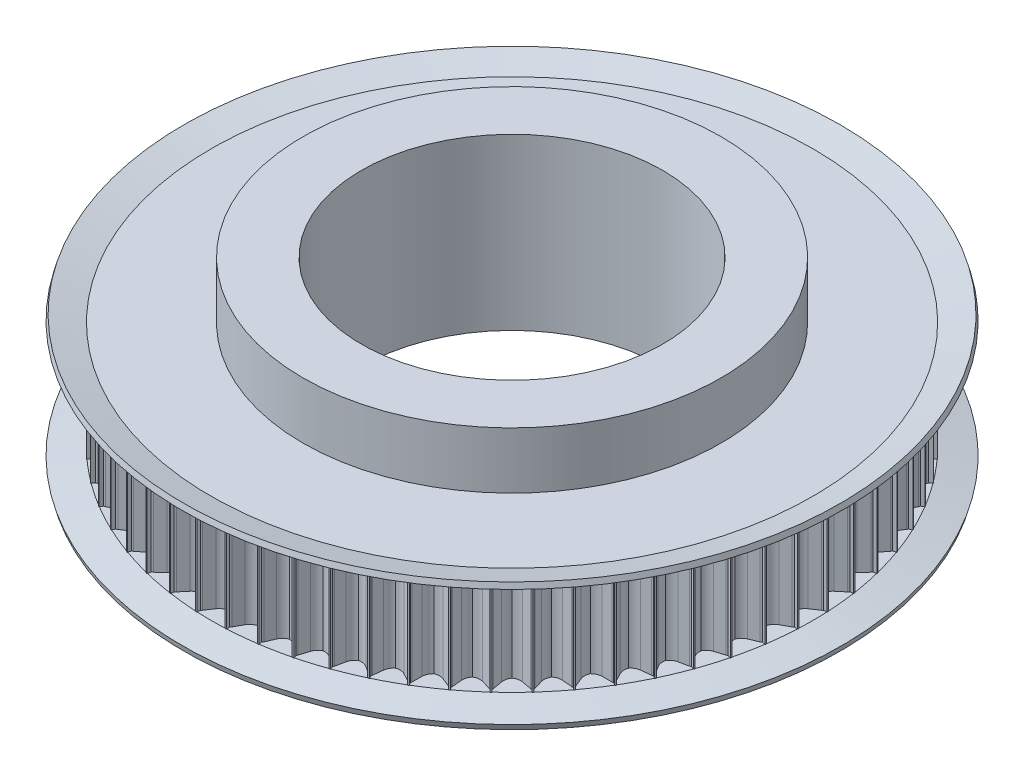
SolidWorks part; units mm, degrees
ref_plane "Front Plane" through (0, 0, 0) normal (0, 0, 1) x (1, 0, 0)
ref_plane "Top Plane" through (0, 0, 0) normal (0, 1, 0) x (1, 0, 0)
ref_plane "Right Plane" through (0, 0, 0) normal (1, 0, 0) x (0, 0, -1)
sketch "Sketch1" plane through (0, 0, 0) normal (0, 1, 0) x (1, 0, 0)
  circle A0 centre (0, 0) radius 40
  circle A1 centre (0, 0) radius 80
  dimension "D1" = 80
  dimension "D2" = 160
extrude "Boss-Extrude1" add sketch "Sketch1" along normal blind 27
sketch "Sketch2" plane through (0, 27, 0) normal (0, 1, 0) x (1, 0, 0)
  line L0 (0, 0) -> (82.1486, 0) construction
  line L8 (76.5582, 2.0076) -> (78.6891, 3.4656)
  line L9 (76.5582, -2.0076) -> (78.6891, -3.4656)
  line L10 (79, 3.75) -> (81.3566, 3.75)
  line L11 (81.3566, 3.75) -> (81.3566, -3.75)
  line L12 (81.3566, -3.75) -> (79, -3.75)
  line L13 (76.3863, -5.5061) -> (78.6499, -4.264)
  line L14 (75.9928, -9.5019) -> (77.9705, -11.1618)
  line L15 (78.9872, -4.0114) -> (81.3324, -4.2424)
  line L16 (81.3324, -4.2424) -> (80.5973, -11.7063)
  line L17 (80.5973, -11.7063) -> (78.252, -11.4753)
  line L18 (75.4788, -12.9667) -> (77.8532, -11.9525)
  line L19 (74.6955, -16.9048) -> (76.501, -18.7505)
  line L20 (78.2136, -11.7342) -> (80.525, -12.1939)
  line L21 (80.525, -12.1939) -> (79.0618, -19.5498)
  line L22 (79.0618, -19.5498) -> (76.7504, -19.0901)
  line L23 (73.8444, -20.3025) -> (76.3068, -19.5259)
  line L24 (72.6789, -24.1448) -> (74.2948, -26.1586)
  line L25 (76.6869, -19.344) -> (78.942, -20.0281)
  line L26 (78.942, -20.0281) -> (76.7649, -27.2051)
  line L27 (76.7649, -27.2051) -> (74.5097, -26.521)
  line L28 (71.4988, -27.4428) -> (74.0255, -26.9112)
  line L29 (69.9623, -31.1523) -> (71.373, -33.3148)
  line L30 (74.4215, -26.7674) -> (76.5988, -27.6693)
  line L31 (76.5988, -27.6693) -> (73.7287, -34.5984)
  line L32 (73.7287, -34.5984) -> (71.5514, -33.6965)
  line L33 (68.4647, -34.3187) -> (71.0313, -34.0374)
  line L34 (66.5719, -37.8598) -> (67.7639, -40.1502)
  line L35 (71.4395, -33.9331) -> (73.5179, -35.044)
  line L36 (73.5179, -35.044) -> (69.9824, -41.6584)
  line L37 (69.9824, -41.6584) -> (67.904, -40.5475)
  line L38 (64.7712, -40.8642) -> (67.353, -40.8358)
  line L39 (62.5405, -44.2027) -> (63.5022, -46.5989)
  line L40 (67.7695, -40.772) -> (69.7289, -42.0813)
  line L41 (69.7289, -42.0813) -> (65.5622, -48.3173)
  line L42 (65.5622, -48.3173) -> (63.6027, -47.0081)
  line L43 (60.4539, -47.0161) -> (63.0261, -47.2409)
  line L44 (57.9067, -50.1199) -> (58.629, -52.5988)
  line L45 (63.4468, -47.2183) -> (65.2685, -48.7133)
  line L46 (65.2685, -48.7133) -> (60.5105, -54.5109)
  line L47 (60.5105, -54.5109) -> (58.6889, -53.0159)
  line L48 (55.5544, -52.7152) -> (58.0922, -53.1911)
  line L49 (52.7152, -55.5544) -> (53.1911, -58.0922)
  line L50 (58.5131, -53.2098) -> (60.1795, -54.8762)
  line L51 (60.1795, -54.8762) -> (54.8762, -60.1795)
  line L52 (54.8762, -60.1795) -> (53.2098, -58.5131)
  line L53 (50.1199, -57.9067) -> (52.5988, -58.629)
  line L54 (47.0161, -60.4539) -> (47.2409, -63.0261)
  line L55 (53.0159, -58.6889) -> (54.5109, -60.5105)
  line L56 (54.5109, -60.5105) -> (48.7133, -65.2685)
  line L57 (48.7133, -65.2685) -> (47.2183, -63.4468)
  line L58 (44.2027, -62.5405) -> (46.5989, -63.5022)
  line L59 (40.8642, -64.7712) -> (40.8358, -67.353)
  line L60 (47.0081, -63.6027) -> (48.3173, -65.5622)
  line L61 (48.3173, -65.5622) -> (42.0813, -69.7289)
  line L62 (42.0813, -69.7289) -> (40.772, -67.7695)
  line L63 (37.8598, -66.5719) -> (40.1502, -67.7639)
  line L64 (34.3187, -68.4647) -> (34.0374, -71.0313)
  line L65 (40.5475, -67.904) -> (41.6584, -69.9824)
  line L66 (41.6584, -69.9824) -> (35.044, -73.5179)
  line L67 (35.044, -73.5179) -> (33.9331, -71.4395)
  line L68 (31.1523, -69.9623) -> (33.3148, -71.373)
  line L69 (27.4428, -71.4988) -> (26.9112, -74.0255)
  line L70 (33.6965, -71.5514) -> (34.5984, -73.7287)
  line L71 (34.5984, -73.7287) -> (27.6693, -76.5988)
  line L72 (27.6693, -76.5988) -> (26.7674, -74.4215)
  line L73 (24.1448, -72.6789) -> (26.1586, -74.2948)
  line L74 (20.3025, -73.8444) -> (19.5259, -76.3068)
  line L75 (26.521, -74.5097) -> (27.2051, -76.7649)
  line L76 (27.2051, -76.7649) -> (20.0281, -78.942)
  line L77 (20.0281, -78.942) -> (19.344, -76.6869)
  line L78 (16.9048, -74.6955) -> (18.7505, -76.501)
  line L79 (12.9667, -75.4788) -> (11.9525, -77.8532)
  line L80 (19.0901, -76.7504) -> (19.5498, -79.0618)
  line L81 (19.5498, -79.0618) -> (12.1939, -80.525)
  line L82 (12.1939, -80.525) -> (11.7342, -78.2136)
  line L83 (9.5019, -75.9928) -> (11.1618, -77.9705)
  line L84 (5.5061, -76.3863) -> (4.264, -78.6499)
  line L85 (11.4753, -78.252) -> (11.7063, -80.5973)
  line L86 (11.7063, -80.5973) -> (4.2424, -81.3324)
  line L87 (4.2424, -81.3324) -> (4.0114, -78.9872)
  line L88 (2.0076, -76.5582) -> (3.4656, -78.6891)
  line L89 (-2.0076, -76.5582) -> (-3.4656, -78.6891)
  line L90 (3.75, -79) -> (3.75, -81.3566)
  line L91 (3.75, -81.3566) -> (-3.75, -81.3566)
  line L92 (-3.75, -81.3566) -> (-3.75, -79)
  line L93 (-5.5061, -76.3863) -> (-4.264, -78.6499)
  line L94 (-9.5019, -75.9928) -> (-11.1618, -77.9705)
  line L95 (-4.0114, -78.9872) -> (-4.2424, -81.3324)
  line L96 (-4.2424, -81.3324) -> (-11.7063, -80.5973)
  line L97 (-11.7063, -80.5973) -> (-11.4753, -78.252)
  line L98 (-12.9667, -75.4788) -> (-11.9525, -77.8532)
  line L99 (-16.9048, -74.6955) -> (-18.7505, -76.501)
  line L100 (-11.7342, -78.2136) -> (-12.1939, -80.525)
  line L101 (-12.1939, -80.525) -> (-19.5498, -79.0618)
  line L102 (-19.5498, -79.0618) -> (-19.0901, -76.7504)
  line L103 (-20.3025, -73.8444) -> (-19.5259, -76.3068)
  line L104 (-24.1448, -72.6789) -> (-26.1586, -74.2948)
  line L105 (-19.344, -76.6869) -> (-20.0281, -78.942)
  line L106 (-20.0281, -78.942) -> (-27.2051, -76.7649)
  line L107 (-27.2051, -76.7649) -> (-26.521, -74.5097)
  line L108 (-27.4428, -71.4988) -> (-26.9112, -74.0255)
  line L109 (-31.1523, -69.9623) -> (-33.3148, -71.373)
  line L110 (-26.7674, -74.4215) -> (-27.6693, -76.5988)
  line L111 (-27.6693, -76.5988) -> (-34.5984, -73.7287)
  line L112 (-34.5984, -73.7287) -> (-33.6965, -71.5514)
  line L113 (-34.3187, -68.4647) -> (-34.0374, -71.0313)
  line L114 (-37.8598, -66.5719) -> (-40.1502, -67.7639)
  line L115 (-33.9331, -71.4395) -> (-35.044, -73.5179)
  line L116 (-35.044, -73.5179) -> (-41.6584, -69.9824)
  line L117 (-41.6584, -69.9824) -> (-40.5475, -67.904)
  line L118 (-40.8642, -64.7712) -> (-40.8358, -67.353)
  line L119 (-44.2027, -62.5405) -> (-46.5989, -63.5022)
  line L120 (-40.772, -67.7695) -> (-42.0813, -69.7289)
  line L121 (-42.0813, -69.7289) -> (-48.3173, -65.5622)
  line L122 (-48.3173, -65.5622) -> (-47.0081, -63.6027)
  line L123 (-47.0161, -60.4539) -> (-47.2409, -63.0261)
  line L124 (-50.1199, -57.9067) -> (-52.5988, -58.629)
  line L125 (-47.2183, -63.4468) -> (-48.7133, -65.2685)
  line L126 (-48.7133, -65.2685) -> (-54.5109, -60.5105)
  line L127 (-54.5109, -60.5105) -> (-53.0159, -58.6889)
  line L128 (-52.7152, -55.5544) -> (-53.1911, -58.0922)
  line L129 (-55.5544, -52.7152) -> (-58.0922, -53.1911)
  line L130 (-53.2098, -58.5131) -> (-54.8762, -60.1795)
  line L131 (-54.8762, -60.1795) -> (-60.1795, -54.8762)
  line L132 (-60.1795, -54.8762) -> (-58.5131, -53.2098)
  line L133 (-57.9067, -50.1199) -> (-58.629, -52.5988)
  line L134 (-60.4539, -47.0161) -> (-63.0261, -47.2409)
  line L135 (-58.6889, -53.0159) -> (-60.5105, -54.5109)
  line L136 (-60.5105, -54.5109) -> (-65.2685, -48.7133)
  line L137 (-65.2685, -48.7133) -> (-63.4468, -47.2183)
  line L138 (-62.5405, -44.2027) -> (-63.5022, -46.5989)
  line L139 (-64.7712, -40.8642) -> (-67.353, -40.8358)
  line L140 (-63.6027, -47.0081) -> (-65.5622, -48.3173)
  line L141 (-65.5622, -48.3173) -> (-69.7289, -42.0813)
  line L142 (-69.7289, -42.0813) -> (-67.7695, -40.772)
  line L143 (-66.5719, -37.8598) -> (-67.7639, -40.1502)
  line L144 (-68.4647, -34.3187) -> (-71.0313, -34.0374)
  line L145 (-67.904, -40.5475) -> (-69.9824, -41.6584)
  line L146 (-69.9824, -41.6584) -> (-73.5179, -35.044)
  line L147 (-73.5179, -35.044) -> (-71.4395, -33.9331)
  line L148 (-69.9623, -31.1523) -> (-71.373, -33.3148)
  line L149 (-71.4988, -27.4428) -> (-74.0255, -26.9112)
  line L150 (-71.5514, -33.6965) -> (-73.7287, -34.5984)
  line L151 (-73.7287, -34.5984) -> (-76.5988, -27.6693)
  line L152 (-76.5988, -27.6693) -> (-74.4215, -26.7674)
  line L153 (-72.6789, -24.1448) -> (-74.2948, -26.1586)
  line L154 (-73.8444, -20.3025) -> (-76.3068, -19.5259)
  line L155 (-74.5097, -26.521) -> (-76.7649, -27.2051)
  line L156 (-76.7649, -27.2051) -> (-78.942, -20.0281)
  line L157 (-78.942, -20.0281) -> (-76.6869, -19.344)
  line L158 (-74.6955, -16.9048) -> (-76.501, -18.7505)
  line L159 (-75.4788, -12.9667) -> (-77.8532, -11.9525)
  line L160 (-76.7504, -19.0901) -> (-79.0618, -19.5498)
  line L161 (-79.0618, -19.5498) -> (-80.525, -12.1939)
  line L162 (-80.525, -12.1939) -> (-78.2136, -11.7342)
  line L163 (-75.9928, -9.5019) -> (-77.9705, -11.1618)
  line L164 (-76.3863, -5.5061) -> (-78.6499, -4.264)
  line L165 (-78.252, -11.4753) -> (-80.5973, -11.7063)
  line L166 (-80.5973, -11.7063) -> (-81.3324, -4.2424)
  line L167 (-81.3324, -4.2424) -> (-78.9872, -4.0114)
  line L168 (-76.5582, -2.0076) -> (-78.6891, -3.4656)
  line L169 (-76.5582, 2.0076) -> (-78.6891, 3.4656)
  line L170 (-79, -3.75) -> (-81.3566, -3.75)
  line L171 (-81.3566, -3.75) -> (-81.3566, 3.75)
  line L172 (-81.3566, 3.75) -> (-79, 3.75)
  line L173 (-76.3863, 5.5061) -> (-78.6499, 4.264)
  line L174 (-75.9928, 9.5019) -> (-77.9705, 11.1618)
  line L175 (-78.9872, 4.0114) -> (-81.3324, 4.2424)
  line L176 (-81.3324, 4.2424) -> (-80.5973, 11.7063)
  line L177 (-80.5973, 11.7063) -> (-78.252, 11.4753)
  line L178 (-75.4788, 12.9667) -> (-77.8532, 11.9525)
  line L179 (-74.6955, 16.9048) -> (-76.501, 18.7505)
  line L180 (-78.2136, 11.7342) -> (-80.525, 12.1939)
  line L181 (-80.525, 12.1939) -> (-79.0618, 19.5498)
  line L182 (-79.0618, 19.5498) -> (-76.7504, 19.0901)
  line L183 (-73.8444, 20.3025) -> (-76.3068, 19.5259)
  line L184 (-72.6789, 24.1448) -> (-74.2948, 26.1586)
  line L185 (-76.6869, 19.344) -> (-78.942, 20.0281)
  line L186 (-78.942, 20.0281) -> (-76.7649, 27.2051)
  line L187 (-76.7649, 27.2051) -> (-74.5097, 26.521)
  line L188 (-71.4988, 27.4428) -> (-74.0255, 26.9112)
  line L189 (-69.9623, 31.1523) -> (-71.373, 33.3148)
  line L190 (-74.4215, 26.7674) -> (-76.5988, 27.6693)
  line L191 (-76.5988, 27.6693) -> (-73.7287, 34.5984)
  line L192 (-73.7287, 34.5984) -> (-71.5514, 33.6965)
  line L193 (-68.4647, 34.3187) -> (-71.0313, 34.0374)
  line L194 (-66.5719, 37.8598) -> (-67.7639, 40.1502)
  line L195 (-71.4395, 33.9331) -> (-73.5179, 35.044)
  line L196 (-73.5179, 35.044) -> (-69.9824, 41.6584)
  line L197 (-69.9824, 41.6584) -> (-67.904, 40.5475)
  line L198 (-64.7712, 40.8642) -> (-67.353, 40.8358)
  line L199 (-62.5405, 44.2027) -> (-63.5022, 46.5989)
  line L200 (-67.7695, 40.772) -> (-69.7289, 42.0813)
  line L201 (-69.7289, 42.0813) -> (-65.5622, 48.3173)
  line L202 (-65.5622, 48.3173) -> (-63.6027, 47.0081)
  line L203 (-60.4539, 47.0161) -> (-63.0261, 47.2409)
  line L204 (-57.9067, 50.1199) -> (-58.629, 52.5988)
  line L205 (-63.4468, 47.2183) -> (-65.2685, 48.7133)
  line L206 (-65.2685, 48.7133) -> (-60.5105, 54.5109)
  line L207 (-60.5105, 54.5109) -> (-58.6889, 53.0159)
  line L208 (-55.5544, 52.7152) -> (-58.0922, 53.1911)
  line L209 (-52.7152, 55.5544) -> (-53.1911, 58.0922)
  line L210 (-58.5131, 53.2098) -> (-60.1795, 54.8762)
  line L211 (-60.1795, 54.8762) -> (-54.8762, 60.1795)
  line L212 (-54.8762, 60.1795) -> (-53.2098, 58.5131)
  line L213 (-50.1199, 57.9067) -> (-52.5988, 58.629)
  line L214 (-47.0161, 60.4539) -> (-47.2409, 63.0261)
  line L215 (-53.0159, 58.6889) -> (-54.5109, 60.5105)
  line L216 (-54.5109, 60.5105) -> (-48.7133, 65.2685)
  line L217 (-48.7133, 65.2685) -> (-47.2183, 63.4468)
  line L218 (-44.2027, 62.5405) -> (-46.5989, 63.5022)
  line L219 (-40.8642, 64.7712) -> (-40.8358, 67.353)
  line L220 (-47.0081, 63.6027) -> (-48.3173, 65.5622)
  line L221 (-48.3173, 65.5622) -> (-42.0813, 69.7289)
  line L222 (-42.0813, 69.7289) -> (-40.772, 67.7695)
  line L223 (-37.8598, 66.5719) -> (-40.1502, 67.7639)
  line L224 (-34.3187, 68.4647) -> (-34.0374, 71.0313)
  line L225 (-40.5475, 67.904) -> (-41.6584, 69.9824)
  line L226 (-41.6584, 69.9824) -> (-35.044, 73.5179)
  line L227 (-35.044, 73.5179) -> (-33.9331, 71.4395)
  line L228 (-31.1523, 69.9623) -> (-33.3148, 71.373)
  line L229 (-27.4428, 71.4988) -> (-26.9112, 74.0255)
  line L230 (-33.6965, 71.5514) -> (-34.5984, 73.7287)
  line L231 (-34.5984, 73.7287) -> (-27.6693, 76.5988)
  line L232 (-27.6693, 76.5988) -> (-26.7674, 74.4215)
  line L233 (-24.1448, 72.6789) -> (-26.1586, 74.2948)
  line L234 (-20.3025, 73.8444) -> (-19.5259, 76.3068)
  line L235 (-26.521, 74.5097) -> (-27.2051, 76.7649)
  line L236 (-27.2051, 76.7649) -> (-20.0281, 78.942)
  line L237 (-20.0281, 78.942) -> (-19.344, 76.6869)
  line L238 (-16.9048, 74.6955) -> (-18.7505, 76.501)
  line L239 (-12.9667, 75.4788) -> (-11.9525, 77.8532)
  line L240 (-19.0901, 76.7504) -> (-19.5498, 79.0618)
  line L241 (-19.5498, 79.0618) -> (-12.1939, 80.525)
  line L242 (-12.1939, 80.525) -> (-11.7342, 78.2136)
  line L243 (-9.5019, 75.9928) -> (-11.1618, 77.9705)
  line L244 (-5.5061, 76.3863) -> (-4.264, 78.6499)
  line L245 (-11.4753, 78.252) -> (-11.7063, 80.5973)
  line L246 (-11.7063, 80.5973) -> (-4.2424, 81.3324)
  line L247 (-4.2424, 81.3324) -> (-4.0114, 78.9872)
  line L248 (-2.0076, 76.5582) -> (-3.4656, 78.6891)
  line L249 (2.0076, 76.5582) -> (3.4656, 78.6891)
  line L250 (-3.75, 79) -> (-3.75, 81.3566)
  line L251 (-3.75, 81.3566) -> (3.75, 81.3566)
  line L252 (3.75, 81.3566) -> (3.75, 79)
  line L253 (5.5061, 76.3863) -> (4.264, 78.6499)
  line L254 (9.5019, 75.9928) -> (11.1618, 77.9705)
  line L255 (4.0114, 78.9872) -> (4.2424, 81.3324)
  line L256 (4.2424, 81.3324) -> (11.7063, 80.5973)
  line L257 (11.7063, 80.5973) -> (11.4753, 78.252)
  line L258 (12.9667, 75.4788) -> (11.9525, 77.8532)
  line L259 (16.9048, 74.6955) -> (18.7505, 76.501)
  line L260 (11.7342, 78.2136) -> (12.1939, 80.525)
  line L261 (12.1939, 80.525) -> (19.5498, 79.0618)
  line L262 (19.5498, 79.0618) -> (19.0901, 76.7504)
  line L263 (20.3025, 73.8444) -> (19.5259, 76.3068)
  line L264 (24.1448, 72.6789) -> (26.1586, 74.2948)
  line L265 (19.344, 76.6869) -> (20.0281, 78.942)
  line L266 (20.0281, 78.942) -> (27.2051, 76.7649)
  line L267 (27.2051, 76.7649) -> (26.521, 74.5097)
  line L268 (27.4428, 71.4988) -> (26.9112, 74.0255)
  line L269 (31.1523, 69.9623) -> (33.3148, 71.373)
  line L270 (26.7674, 74.4215) -> (27.6693, 76.5988)
  line L271 (27.6693, 76.5988) -> (34.5984, 73.7287)
  line L272 (34.5984, 73.7287) -> (33.6965, 71.5514)
  line L273 (34.3187, 68.4647) -> (34.0374, 71.0313)
  line L274 (37.8598, 66.5719) -> (40.1502, 67.7639)
  line L275 (33.9331, 71.4395) -> (35.044, 73.5179)
  line L276 (35.044, 73.5179) -> (41.6584, 69.9824)
  line L277 (41.6584, 69.9824) -> (40.5475, 67.904)
  line L278 (40.8642, 64.7712) -> (40.8358, 67.353)
  line L279 (44.2027, 62.5405) -> (46.5989, 63.5022)
  line L280 (40.772, 67.7695) -> (42.0813, 69.7289)
  line L281 (42.0813, 69.7289) -> (48.3173, 65.5622)
  line L282 (48.3173, 65.5622) -> (47.0081, 63.6027)
  line L283 (47.0161, 60.4539) -> (47.2409, 63.0261)
  line L284 (50.1199, 57.9067) -> (52.5988, 58.629)
  line L285 (47.2183, 63.4468) -> (48.7133, 65.2685)
  line L286 (48.7133, 65.2685) -> (54.5109, 60.5105)
  line L287 (54.5109, 60.5105) -> (53.0159, 58.6889)
  line L288 (52.7152, 55.5544) -> (53.1911, 58.0922)
  line L289 (55.5544, 52.7152) -> (58.0922, 53.1911)
  line L290 (53.2098, 58.5131) -> (54.8762, 60.1795)
  line L291 (54.8762, 60.1795) -> (60.1795, 54.8762)
  line L292 (60.1795, 54.8762) -> (58.5131, 53.2098)
  line L293 (57.9067, 50.1199) -> (58.629, 52.5988)
  line L294 (60.4539, 47.0161) -> (63.0261, 47.2409)
  line L295 (58.6889, 53.0159) -> (60.5105, 54.5109)
  line L296 (60.5105, 54.5109) -> (65.2685, 48.7133)
  line L297 (65.2685, 48.7133) -> (63.4468, 47.2183)
  line L298 (62.5405, 44.2027) -> (63.5022, 46.5989)
  line L299 (64.7712, 40.8642) -> (67.353, 40.8358)
  line L300 (63.6027, 47.0081) -> (65.5622, 48.3173)
  line L301 (65.5622, 48.3173) -> (69.7289, 42.0813)
  line L302 (69.7289, 42.0813) -> (67.7695, 40.772)
  line L303 (66.5719, 37.8598) -> (67.7639, 40.1502)
  line L304 (68.4647, 34.3187) -> (71.0313, 34.0374)
  line L305 (67.904, 40.5475) -> (69.9824, 41.6584)
  line L306 (69.9824, 41.6584) -> (73.5179, 35.044)
  line L307 (73.5179, 35.044) -> (71.4395, 33.9331)
  line L308 (69.9623, 31.1523) -> (71.373, 33.3148)
  line L309 (71.4988, 27.4428) -> (74.0255, 26.9112)
  line L310 (71.5514, 33.6965) -> (73.7287, 34.5984)
  line L311 (73.7287, 34.5984) -> (76.5988, 27.6693)
  line L312 (76.5988, 27.6693) -> (74.4215, 26.7674)
  line L313 (72.6789, 24.1448) -> (74.2948, 26.1586)
  line L314 (73.8444, 20.3025) -> (76.3068, 19.5259)
  line L315 (74.5097, 26.521) -> (76.7649, 27.2051)
  line L316 (76.7649, 27.2051) -> (78.942, 20.0281)
  line L317 (78.942, 20.0281) -> (76.6869, 19.344)
  line L318 (74.6955, 16.9048) -> (76.501, 18.7505)
  line L319 (75.4788, 12.9667) -> (77.8532, 11.9525)
  line L320 (76.7504, 19.0901) -> (79.0618, 19.5498)
  line L321 (79.0618, 19.5498) -> (80.525, 12.1939)
  line L322 (80.525, 12.1939) -> (78.2136, 11.7342)
  line L323 (75.9928, 9.5019) -> (77.9705, 11.1618)
  line L324 (76.3863, 5.5061) -> (78.6499, 4.264)
  line L325 (78.252, 11.4753) -> (80.5973, 11.7063)
  line L326 (80.5973, 11.7063) -> (81.3324, 4.2424)
  line L327 (81.3324, 4.2424) -> (78.9872, 4.0114)
  arc A4 (75.289, 0) -> (76.5582, -2.0076) centre (78.2523, 0.4683) ccw
  arc A5 (79, -3.75) -> (78.6891, -3.4656) centre (77.8421, -4.7036) ccw
  arc A6 (79, 3.75) -> (78.6891, 3.4656) centre (77.8421, 4.7036) cw
  arc A7 (75.289, 0) -> (76.5582, 2.0076) centre (78.2523, -0.4683) cw
  arc A8 (74.9265, -7.3796) -> (75.9928, -9.5019) centre (77.9214, -7.204) ccw
  arc A9 (78.252, -11.4753) -> (77.9705, -11.1618) centre (77.0062, -12.3108) ccw
  arc A10 (78.9872, -4.0114) -> (78.6499, -4.264) centre (77.9283, -2.9489) cw
  arc A11 (74.9265, -7.3796) -> (76.3863, -5.5061) centre (77.8295, -8.1361) cw
  arc A12 (73.8424, -14.6882) -> (74.6955, -16.9048) centre (76.84, -14.8069) ccw
  arc A13 (76.7504, -19.0901) -> (76.501, -18.7505) centre (75.4288, -19.7994) ccw
  arc A14 (78.2136, -11.7342) -> (77.8532, -11.9525) centre (77.264, -10.5731) cw
  arc A15 (73.8424, -14.6882) -> (75.4788, -12.9667) centre (76.6573, -15.7256) cw
  arc A16 (72.0471, -21.8553) -> (72.6789, -24.1448) centre (75.0187, -22.2673) ccw
  arc A17 (74.5097, -26.521) -> (74.2948, -26.1586) centre (73.1249, -27.0974) ccw
  arc A18 (76.6869, -19.344) -> (76.3068, -19.5259) centre (75.8556, -18.0953) cw
  arc A19 (72.0471, -21.8553) -> (73.8444, -20.3025) centre (74.7468, -23.1636) cw
  arc A20 (69.558, -28.8119) -> (69.9623, -31.1523) centre (72.4749, -29.5132) ccw
  arc A21 (71.5514, -33.6965) -> (71.373, -33.3148) centre (70.1168, -34.1344) ccw
  arc A22 (74.4215, -26.7674) -> (74.0255, -26.9112) centre (73.7167, -25.4434) cw
  arc A23 (69.558, -28.8119) -> (71.4988, -27.4428) centre (72.1164, -30.3785) cw
  arc A24 (66.399, -35.491) -> (66.5719, -37.8598) centre (69.2331, -36.4748) ccw
  arc A25 (67.904, -40.5475) -> (67.7639, -40.1502) centre (66.4334, -40.8427) ccw
  arc A26 (71.4395, -33.9331) -> (71.0313, -34.0374) centre (70.8679, -32.5463) cw
  arc A27 (66.399, -35.491) -> (68.4647, -34.3187) centre (68.7916, -37.3009) cw
  arc A28 (62.6005, -41.8283) -> (62.5405, -44.2027) centre (65.3246, -43.0852) ccw
  arc A29 (63.6027, -47.0081) -> (63.5022, -46.5989) centre (62.1102, -47.1576) ccw
  arc A30 (67.7695, -40.772) -> (67.353, -40.8358) centre (67.3365, -39.3359) cw
  arc A31 (62.6005, -41.8283) -> (64.7712, -40.8642) centre (64.8042, -43.864) cw
  arc A32 (58.1992, -47.7629) -> (57.9067, -50.1199) centre (60.7869, -49.2807) ccw
  arc A33 (58.6889, -53.0159) -> (58.629, -52.5988) centre (57.1889, -53.0184) ccw
  arc A34 (63.4468, -47.2183) -> (63.0261, -47.2409) centre (63.1567, -45.7466) cw
  arc A35 (58.1992, -47.7629) -> (60.4539, -47.0161) centre (60.1927, -50.0047) cw
  arc A36 (53.2374, -53.2374) -> (52.7152, -55.5544) centre (55.6639, -55.0015) ccw
  arc A37 (53.2098, -58.5131) -> (53.1911, -58.0922) centre (51.7168, -58.3686) ccw
  arc A38 (58.5131, -53.2098) -> (58.0922, -53.1911) centre (58.3686, -51.7168) cw
  arc A39 (53.2374, -53.2374) -> (55.5544, -52.7152) centre (55.0015, -55.6639) cw
  arc A40 (47.7629, -58.1992) -> (47.0161, -60.4539) centre (50.0047, -60.1927) ccw
  arc A41 (47.2183, -63.4468) -> (47.2409, -63.0261) centre (45.7466, -63.1567) ccw
  arc A42 (53.0159, -58.6889) -> (52.5988, -58.629) centre (53.0184, -57.1889) cw
  arc A43 (47.7629, -58.1992) -> (50.1199, -57.9067) centre (49.2807, -60.7869) cw
  arc A44 (41.8283, -62.6005) -> (40.8642, -64.7712) centre (43.864, -64.8042) ccw
  arc A45 (40.772, -67.7695) -> (40.8358, -67.353) centre (39.3359, -67.3365) ccw
  arc A46 (47.0081, -63.6027) -> (46.5989, -63.5022) centre (47.1576, -62.1102) cw
  arc A47 (41.8283, -62.6005) -> (44.2027, -62.5405) centre (43.0852, -65.3246) cw
  arc A48 (35.491, -66.399) -> (34.3187, -68.4647) centre (37.3009, -68.7916) ccw
  arc A49 (33.9331, -71.4395) -> (34.0374, -71.0313) centre (32.5463, -70.8679) ccw
  arc A50 (40.5475, -67.904) -> (40.1502, -67.7639) centre (40.8427, -66.4334) cw
  arc A51 (35.491, -66.399) -> (37.8598, -66.5719) centre (36.4748, -69.2331) cw
  arc A52 (28.8119, -69.558) -> (27.4428, -71.4988) centre (30.3785, -72.1164) ccw
  arc A53 (26.7674, -74.4215) -> (26.9112, -74.0255) centre (25.4434, -73.7167) ccw
  arc A54 (33.6965, -71.5514) -> (33.3148, -71.373) centre (34.1344, -70.1168) cw
  arc A55 (28.8119, -69.558) -> (31.1523, -69.9623) centre (29.5132, -72.4749) cw
  arc A56 (21.8553, -72.0471) -> (20.3025, -73.8444) centre (23.1636, -74.7468) ccw
  arc A57 (19.344, -76.6869) -> (19.5259, -76.3068) centre (18.0953, -75.8556) ccw
  arc A58 (26.521, -74.5097) -> (26.1586, -74.2948) centre (27.0974, -73.1249) cw
  arc A59 (21.8553, -72.0471) -> (24.1448, -72.6789) centre (22.2673, -75.0187) cw
  arc A60 (14.6882, -73.8424) -> (12.9667, -75.4788) centre (15.7256, -76.6573) ccw
  arc A61 (11.7342, -78.2136) -> (11.9525, -77.8532) centre (10.5731, -77.264) ccw
  arc A62 (19.0901, -76.7504) -> (18.7505, -76.501) centre (19.7994, -75.4288) cw
  arc A63 (14.6882, -73.8424) -> (16.9048, -74.6955) centre (14.8069, -76.84) cw
  arc A64 (7.3796, -74.9265) -> (5.5061, -76.3863) centre (8.1361, -77.8295) ccw
  arc A65 (4.0114, -78.9872) -> (4.264, -78.6499) centre (2.9489, -77.9283) ccw
  arc A66 (11.4753, -78.252) -> (11.1618, -77.9705) centre (12.3108, -77.0062) cw
  arc A67 (7.3796, -74.9265) -> (9.5019, -75.9928) centre (7.204, -77.9214) cw
  arc A68 (0, -75.289) -> (-2.0076, -76.5582) centre (0.4683, -78.2523) ccw
  arc A69 (-3.75, -79) -> (-3.4656, -78.6891) centre (-4.7036, -77.8421) ccw
  arc A70 (3.75, -79) -> (3.4656, -78.6891) centre (4.7036, -77.8421) cw
  arc A71 (0, -75.289) -> (2.0076, -76.5582) centre (-0.4683, -78.2523) cw
  arc A72 (-7.3796, -74.9265) -> (-9.5019, -75.9928) centre (-7.204, -77.9214) ccw
  arc A73 (-11.4753, -78.252) -> (-11.1618, -77.9705) centre (-12.3108, -77.0062) ccw
  arc A74 (-4.0114, -78.9872) -> (-4.264, -78.6499) centre (-2.9489, -77.9283) cw
  arc A75 (-7.3796, -74.9265) -> (-5.5061, -76.3863) centre (-8.1361, -77.8295) cw
  arc A76 (-14.6882, -73.8424) -> (-16.9048, -74.6955) centre (-14.8069, -76.84) ccw
  arc A77 (-19.0901, -76.7504) -> (-18.7505, -76.501) centre (-19.7994, -75.4288) ccw
  arc A78 (-11.7342, -78.2136) -> (-11.9525, -77.8532) centre (-10.5731, -77.264) cw
  arc A79 (-14.6882, -73.8424) -> (-12.9667, -75.4788) centre (-15.7256, -76.6573) cw
  arc A80 (-21.8553, -72.0471) -> (-24.1448, -72.6789) centre (-22.2673, -75.0187) ccw
  arc A81 (-26.521, -74.5097) -> (-26.1586, -74.2948) centre (-27.0974, -73.1249) ccw
  arc A82 (-19.344, -76.6869) -> (-19.5259, -76.3068) centre (-18.0953, -75.8556) cw
  arc A83 (-21.8553, -72.0471) -> (-20.3025, -73.8444) centre (-23.1636, -74.7468) cw
  arc A84 (-28.8119, -69.558) -> (-31.1523, -69.9623) centre (-29.5132, -72.4749) ccw
  arc A85 (-33.6965, -71.5514) -> (-33.3148, -71.373) centre (-34.1344, -70.1168) ccw
  arc A86 (-26.7674, -74.4215) -> (-26.9112, -74.0255) centre (-25.4434, -73.7167) cw
  arc A87 (-28.8119, -69.558) -> (-27.4428, -71.4988) centre (-30.3785, -72.1164) cw
  arc A88 (-35.491, -66.399) -> (-37.8598, -66.5719) centre (-36.4748, -69.2331) ccw
  arc A89 (-40.5475, -67.904) -> (-40.1502, -67.7639) centre (-40.8427, -66.4334) ccw
  arc A90 (-33.9331, -71.4395) -> (-34.0374, -71.0313) centre (-32.5463, -70.8679) cw
  arc A91 (-35.491, -66.399) -> (-34.3187, -68.4647) centre (-37.3009, -68.7916) cw
  arc A92 (-41.8283, -62.6005) -> (-44.2027, -62.5405) centre (-43.0852, -65.3246) ccw
  arc A93 (-47.0081, -63.6027) -> (-46.5989, -63.5022) centre (-47.1576, -62.1102) ccw
  arc A94 (-40.772, -67.7695) -> (-40.8358, -67.353) centre (-39.3359, -67.3365) cw
  arc A95 (-41.8283, -62.6005) -> (-40.8642, -64.7712) centre (-43.864, -64.8042) cw
  arc A96 (-47.7629, -58.1992) -> (-50.1199, -57.9067) centre (-49.2807, -60.7869) ccw
  arc A97 (-53.0159, -58.6889) -> (-52.5988, -58.629) centre (-53.0184, -57.1889) ccw
  arc A98 (-47.2183, -63.4468) -> (-47.2409, -63.0261) centre (-45.7466, -63.1567) cw
  arc A99 (-47.7629, -58.1992) -> (-47.0161, -60.4539) centre (-50.0047, -60.1927) cw
  arc A100 (-53.2374, -53.2374) -> (-55.5544, -52.7152) centre (-55.0015, -55.6639) ccw
  arc A101 (-58.5131, -53.2098) -> (-58.0922, -53.1911) centre (-58.3686, -51.7168) ccw
  arc A102 (-53.2098, -58.5131) -> (-53.1911, -58.0922) centre (-51.7168, -58.3686) cw
  arc A103 (-53.2374, -53.2374) -> (-52.7152, -55.5544) centre (-55.6639, -55.0015) cw
  arc A104 (-58.1992, -47.7629) -> (-60.4539, -47.0161) centre (-60.1927, -50.0047) ccw
  arc A105 (-63.4468, -47.2183) -> (-63.0261, -47.2409) centre (-63.1567, -45.7466) ccw
  arc A106 (-58.6889, -53.0159) -> (-58.629, -52.5988) centre (-57.1889, -53.0184) cw
  arc A107 (-58.1992, -47.7629) -> (-57.9067, -50.1199) centre (-60.7869, -49.2807) cw
  arc A108 (-62.6005, -41.8283) -> (-64.7712, -40.8642) centre (-64.8042, -43.864) ccw
  arc A109 (-67.7695, -40.772) -> (-67.353, -40.8358) centre (-67.3365, -39.3359) ccw
  arc A110 (-63.6027, -47.0081) -> (-63.5022, -46.5989) centre (-62.1102, -47.1576) cw
  arc A111 (-62.6005, -41.8283) -> (-62.5405, -44.2027) centre (-65.3246, -43.0852) cw
  arc A112 (-66.399, -35.491) -> (-68.4647, -34.3187) centre (-68.7916, -37.3009) ccw
  arc A113 (-71.4395, -33.9331) -> (-71.0313, -34.0374) centre (-70.8679, -32.5463) ccw
  arc A114 (-67.904, -40.5475) -> (-67.7639, -40.1502) centre (-66.4334, -40.8427) cw
  arc A115 (-66.399, -35.491) -> (-66.5719, -37.8598) centre (-69.2331, -36.4748) cw
  arc A116 (-69.558, -28.8119) -> (-71.4988, -27.4428) centre (-72.1164, -30.3785) ccw
  arc A117 (-74.4215, -26.7674) -> (-74.0255, -26.9112) centre (-73.7167, -25.4434) ccw
  arc A118 (-71.5514, -33.6965) -> (-71.373, -33.3148) centre (-70.1168, -34.1344) cw
  arc A119 (-69.558, -28.8119) -> (-69.9623, -31.1523) centre (-72.4749, -29.5132) cw
  arc A120 (-72.0471, -21.8553) -> (-73.8444, -20.3025) centre (-74.7468, -23.1636) ccw
  arc A121 (-76.6869, -19.344) -> (-76.3068, -19.5259) centre (-75.8556, -18.0953) ccw
  arc A122 (-74.5097, -26.521) -> (-74.2948, -26.1586) centre (-73.1249, -27.0974) cw
  arc A123 (-72.0471, -21.8553) -> (-72.6789, -24.1448) centre (-75.0187, -22.2673) cw
  arc A124 (-73.8424, -14.6882) -> (-75.4788, -12.9667) centre (-76.6573, -15.7256) ccw
  arc A125 (-78.2136, -11.7342) -> (-77.8532, -11.9525) centre (-77.264, -10.5731) ccw
  arc A126 (-76.7504, -19.0901) -> (-76.501, -18.7505) centre (-75.4288, -19.7994) cw
  arc A127 (-73.8424, -14.6882) -> (-74.6955, -16.9048) centre (-76.84, -14.8069) cw
  arc A128 (-74.9265, -7.3796) -> (-76.3863, -5.5061) centre (-77.8295, -8.1361) ccw
  arc A129 (-78.9872, -4.0114) -> (-78.6499, -4.264) centre (-77.9283, -2.9489) ccw
  arc A130 (-78.252, -11.4753) -> (-77.9705, -11.1618) centre (-77.0062, -12.3108) cw
  arc A131 (-74.9265, -7.3796) -> (-75.9928, -9.5019) centre (-77.9214, -7.204) cw
  arc A132 (-75.289, 0) -> (-76.5582, 2.0076) centre (-78.2523, -0.4683) ccw
  arc A133 (-79, 3.75) -> (-78.6891, 3.4656) centre (-77.8421, 4.7036) ccw
  arc A134 (-79, -3.75) -> (-78.6891, -3.4656) centre (-77.8421, -4.7036) cw
  arc A135 (-75.289, 0) -> (-76.5582, -2.0076) centre (-78.2523, 0.4683) cw
  arc A136 (-74.9265, 7.3796) -> (-75.9928, 9.5019) centre (-77.9214, 7.204) ccw
  arc A137 (-78.252, 11.4753) -> (-77.9705, 11.1618) centre (-77.0062, 12.3108) ccw
  arc A138 (-78.9872, 4.0114) -> (-78.6499, 4.264) centre (-77.9283, 2.9489) cw
  arc A139 (-74.9265, 7.3796) -> (-76.3863, 5.5061) centre (-77.8295, 8.1361) cw
  arc A140 (-73.8424, 14.6882) -> (-74.6955, 16.9048) centre (-76.84, 14.8069) ccw
  arc A141 (-76.7504, 19.0901) -> (-76.501, 18.7505) centre (-75.4288, 19.7994) ccw
  arc A142 (-78.2136, 11.7342) -> (-77.8532, 11.9525) centre (-77.264, 10.5731) cw
  arc A143 (-73.8424, 14.6882) -> (-75.4788, 12.9667) centre (-76.6573, 15.7256) cw
  arc A144 (-72.0471, 21.8553) -> (-72.6789, 24.1448) centre (-75.0187, 22.2673) ccw
  arc A145 (-74.5097, 26.521) -> (-74.2948, 26.1586) centre (-73.1249, 27.0974) ccw
  arc A146 (-76.6869, 19.344) -> (-76.3068, 19.5259) centre (-75.8556, 18.0953) cw
  arc A147 (-72.0471, 21.8553) -> (-73.8444, 20.3025) centre (-74.7468, 23.1636) cw
  arc A148 (-69.558, 28.8119) -> (-69.9623, 31.1523) centre (-72.4749, 29.5132) ccw
  arc A149 (-71.5514, 33.6965) -> (-71.373, 33.3148) centre (-70.1168, 34.1344) ccw
  arc A150 (-74.4215, 26.7674) -> (-74.0255, 26.9112) centre (-73.7167, 25.4434) cw
  arc A151 (-69.558, 28.8119) -> (-71.4988, 27.4428) centre (-72.1164, 30.3785) cw
  arc A152 (-66.399, 35.491) -> (-66.5719, 37.8598) centre (-69.2331, 36.4748) ccw
  arc A153 (-67.904, 40.5475) -> (-67.7639, 40.1502) centre (-66.4334, 40.8427) ccw
  arc A154 (-71.4395, 33.9331) -> (-71.0313, 34.0374) centre (-70.8679, 32.5463) cw
  arc A155 (-66.399, 35.491) -> (-68.4647, 34.3187) centre (-68.7916, 37.3009) cw
  arc A156 (-62.6005, 41.8283) -> (-62.5405, 44.2027) centre (-65.3246, 43.0852) ccw
  arc A157 (-63.6027, 47.0081) -> (-63.5022, 46.5989) centre (-62.1102, 47.1576) ccw
  arc A158 (-67.7695, 40.772) -> (-67.353, 40.8358) centre (-67.3365, 39.3359) cw
  arc A159 (-62.6005, 41.8283) -> (-64.7712, 40.8642) centre (-64.8042, 43.864) cw
  arc A160 (-58.1992, 47.7629) -> (-57.9067, 50.1199) centre (-60.7869, 49.2807) ccw
  arc A161 (-58.6889, 53.0159) -> (-58.629, 52.5988) centre (-57.1889, 53.0184) ccw
  arc A162 (-63.4468, 47.2183) -> (-63.0261, 47.2409) centre (-63.1567, 45.7466) cw
  arc A163 (-58.1992, 47.7629) -> (-60.4539, 47.0161) centre (-60.1927, 50.0047) cw
  arc A164 (-53.2374, 53.2374) -> (-52.7152, 55.5544) centre (-55.6639, 55.0015) ccw
  arc A165 (-53.2098, 58.5131) -> (-53.1911, 58.0922) centre (-51.7168, 58.3686) ccw
  arc A166 (-58.5131, 53.2098) -> (-58.0922, 53.1911) centre (-58.3686, 51.7168) cw
  arc A167 (-53.2374, 53.2374) -> (-55.5544, 52.7152) centre (-55.0015, 55.6639) cw
  arc A168 (-47.7629, 58.1992) -> (-47.0161, 60.4539) centre (-50.0047, 60.1927) ccw
  arc A169 (-47.2183, 63.4468) -> (-47.2409, 63.0261) centre (-45.7466, 63.1567) ccw
  arc A170 (-53.0159, 58.6889) -> (-52.5988, 58.629) centre (-53.0184, 57.1889) cw
  arc A171 (-47.7629, 58.1992) -> (-50.1199, 57.9067) centre (-49.2807, 60.7869) cw
  arc A172 (-41.8283, 62.6005) -> (-40.8642, 64.7712) centre (-43.864, 64.8042) ccw
  arc A173 (-40.772, 67.7695) -> (-40.8358, 67.353) centre (-39.3359, 67.3365) ccw
  arc A174 (-47.0081, 63.6027) -> (-46.5989, 63.5022) centre (-47.1576, 62.1102) cw
  arc A175 (-41.8283, 62.6005) -> (-44.2027, 62.5405) centre (-43.0852, 65.3246) cw
  arc A176 (-35.491, 66.399) -> (-34.3187, 68.4647) centre (-37.3009, 68.7916) ccw
  arc A177 (-33.9331, 71.4395) -> (-34.0374, 71.0313) centre (-32.5463, 70.8679) ccw
  arc A178 (-40.5475, 67.904) -> (-40.1502, 67.7639) centre (-40.8427, 66.4334) cw
  arc A179 (-35.491, 66.399) -> (-37.8598, 66.5719) centre (-36.4748, 69.2331) cw
  arc A180 (-28.8119, 69.558) -> (-27.4428, 71.4988) centre (-30.3785, 72.1164) ccw
  arc A181 (-26.7674, 74.4215) -> (-26.9112, 74.0255) centre (-25.4434, 73.7167) ccw
  arc A182 (-33.6965, 71.5514) -> (-33.3148, 71.373) centre (-34.1344, 70.1168) cw
  arc A183 (-28.8119, 69.558) -> (-31.1523, 69.9623) centre (-29.5132, 72.4749) cw
  arc A184 (-21.8553, 72.0471) -> (-20.3025, 73.8444) centre (-23.1636, 74.7468) ccw
  arc A185 (-19.344, 76.6869) -> (-19.5259, 76.3068) centre (-18.0953, 75.8556) ccw
  arc A186 (-26.521, 74.5097) -> (-26.1586, 74.2948) centre (-27.0974, 73.1249) cw
  arc A187 (-21.8553, 72.0471) -> (-24.1448, 72.6789) centre (-22.2673, 75.0187) cw
  arc A188 (-14.6882, 73.8424) -> (-12.9667, 75.4788) centre (-15.7256, 76.6573) ccw
  arc A189 (-11.7342, 78.2136) -> (-11.9525, 77.8532) centre (-10.5731, 77.264) ccw
  arc A190 (-19.0901, 76.7504) -> (-18.7505, 76.501) centre (-19.7994, 75.4288) cw
  arc A191 (-14.6882, 73.8424) -> (-16.9048, 74.6955) centre (-14.8069, 76.84) cw
  arc A192 (-7.3796, 74.9265) -> (-5.5061, 76.3863) centre (-8.1361, 77.8295) ccw
  arc A193 (-4.0114, 78.9872) -> (-4.264, 78.6499) centre (-2.9489, 77.9283) ccw
  arc A194 (-11.4753, 78.252) -> (-11.1618, 77.9705) centre (-12.3108, 77.0062) cw
  arc A195 (-7.3796, 74.9265) -> (-9.5019, 75.9928) centre (-7.204, 77.9214) cw
  arc A196 (0, 75.289) -> (2.0076, 76.5582) centre (-0.4683, 78.2523) ccw
  arc A197 (3.75, 79) -> (3.4656, 78.6891) centre (4.7036, 77.8421) ccw
  arc A198 (-3.75, 79) -> (-3.4656, 78.6891) centre (-4.7036, 77.8421) cw
  arc A199 (0, 75.289) -> (-2.0076, 76.5582) centre (0.4683, 78.2523) cw
  arc A200 (7.3796, 74.9265) -> (9.5019, 75.9928) centre (7.204, 77.9214) ccw
  arc A201 (11.4753, 78.252) -> (11.1618, 77.9705) centre (12.3108, 77.0062) ccw
  arc A202 (4.0114, 78.9872) -> (4.264, 78.6499) centre (2.9489, 77.9283) cw
  arc A203 (7.3796, 74.9265) -> (5.5061, 76.3863) centre (8.1361, 77.8295) cw
  arc A204 (14.6882, 73.8424) -> (16.9048, 74.6955) centre (14.8069, 76.84) ccw
  arc A205 (19.0901, 76.7504) -> (18.7505, 76.501) centre (19.7994, 75.4288) ccw
  arc A206 (11.7342, 78.2136) -> (11.9525, 77.8532) centre (10.5731, 77.264) cw
  arc A207 (14.6882, 73.8424) -> (12.9667, 75.4788) centre (15.7256, 76.6573) cw
  arc A208 (21.8553, 72.0471) -> (24.1448, 72.6789) centre (22.2673, 75.0187) ccw
  arc A209 (26.521, 74.5097) -> (26.1586, 74.2948) centre (27.0974, 73.1249) ccw
  arc A210 (19.344, 76.6869) -> (19.5259, 76.3068) centre (18.0953, 75.8556) cw
  arc A211 (21.8553, 72.0471) -> (20.3025, 73.8444) centre (23.1636, 74.7468) cw
  arc A212 (28.8119, 69.558) -> (31.1523, 69.9623) centre (29.5132, 72.4749) ccw
  arc A213 (33.6965, 71.5514) -> (33.3148, 71.373) centre (34.1344, 70.1168) ccw
  arc A214 (26.7674, 74.4215) -> (26.9112, 74.0255) centre (25.4434, 73.7167) cw
  arc A215 (28.8119, 69.558) -> (27.4428, 71.4988) centre (30.3785, 72.1164) cw
  arc A216 (35.491, 66.399) -> (37.8598, 66.5719) centre (36.4748, 69.2331) ccw
  arc A217 (40.5475, 67.904) -> (40.1502, 67.7639) centre (40.8427, 66.4334) ccw
  arc A218 (33.9331, 71.4395) -> (34.0374, 71.0313) centre (32.5463, 70.8679) cw
  arc A219 (35.491, 66.399) -> (34.3187, 68.4647) centre (37.3009, 68.7916) cw
  arc A220 (41.8283, 62.6005) -> (44.2027, 62.5405) centre (43.0852, 65.3246) ccw
  arc A221 (47.0081, 63.6027) -> (46.5989, 63.5022) centre (47.1576, 62.1102) ccw
  arc A222 (40.772, 67.7695) -> (40.8358, 67.353) centre (39.3359, 67.3365) cw
  arc A223 (41.8283, 62.6005) -> (40.8642, 64.7712) centre (43.864, 64.8042) cw
  arc A224 (47.7629, 58.1992) -> (50.1199, 57.9067) centre (49.2807, 60.7869) ccw
  arc A225 (53.0159, 58.6889) -> (52.5988, 58.629) centre (53.0184, 57.1889) ccw
  arc A226 (47.2183, 63.4468) -> (47.2409, 63.0261) centre (45.7466, 63.1567) cw
  arc A227 (47.7629, 58.1992) -> (47.0161, 60.4539) centre (50.0047, 60.1927) cw
  arc A228 (53.2374, 53.2374) -> (55.5544, 52.7152) centre (55.0015, 55.6639) ccw
  arc A229 (58.5131, 53.2098) -> (58.0922, 53.1911) centre (58.3686, 51.7168) ccw
  arc A230 (53.2098, 58.5131) -> (53.1911, 58.0922) centre (51.7168, 58.3686) cw
  arc A231 (53.2374, 53.2374) -> (52.7152, 55.5544) centre (55.6639, 55.0015) cw
  arc A232 (58.1992, 47.7629) -> (60.4539, 47.0161) centre (60.1927, 50.0047) ccw
  arc A233 (63.4468, 47.2183) -> (63.0261, 47.2409) centre (63.1567, 45.7466) ccw
  arc A234 (58.6889, 53.0159) -> (58.629, 52.5988) centre (57.1889, 53.0184) cw
  arc A235 (58.1992, 47.7629) -> (57.9067, 50.1199) centre (60.7869, 49.2807) cw
  arc A236 (62.6005, 41.8283) -> (64.7712, 40.8642) centre (64.8042, 43.864) ccw
  arc A237 (67.7695, 40.772) -> (67.353, 40.8358) centre (67.3365, 39.3359) ccw
  arc A238 (63.6027, 47.0081) -> (63.5022, 46.5989) centre (62.1102, 47.1576) cw
  arc A239 (62.6005, 41.8283) -> (62.5405, 44.2027) centre (65.3246, 43.0852) cw
  arc A240 (66.399, 35.491) -> (68.4647, 34.3187) centre (68.7916, 37.3009) ccw
  arc A241 (71.4395, 33.9331) -> (71.0313, 34.0374) centre (70.8679, 32.5463) ccw
  arc A242 (67.904, 40.5475) -> (67.7639, 40.1502) centre (66.4334, 40.8427) cw
  arc A243 (66.399, 35.491) -> (66.5719, 37.8598) centre (69.2331, 36.4748) cw
  arc A244 (69.558, 28.8119) -> (71.4988, 27.4428) centre (72.1164, 30.3785) ccw
  arc A245 (74.4215, 26.7674) -> (74.0255, 26.9112) centre (73.7167, 25.4434) ccw
  arc A246 (71.5514, 33.6965) -> (71.373, 33.3148) centre (70.1168, 34.1344) cw
  arc A247 (69.558, 28.8119) -> (69.9623, 31.1523) centre (72.4749, 29.5132) cw
  arc A248 (72.0471, 21.8553) -> (73.8444, 20.3025) centre (74.7468, 23.1636) ccw
  arc A249 (76.6869, 19.344) -> (76.3068, 19.5259) centre (75.8556, 18.0953) ccw
  arc A250 (74.5097, 26.521) -> (74.2948, 26.1586) centre (73.1249, 27.0974) cw
  arc A251 (72.0471, 21.8553) -> (72.6789, 24.1448) centre (75.0187, 22.2673) cw
  arc A252 (73.8424, 14.6882) -> (75.4788, 12.9667) centre (76.6573, 15.7256) ccw
  arc A253 (78.2136, 11.7342) -> (77.8532, 11.9525) centre (77.264, 10.5731) ccw
  arc A254 (76.7504, 19.0901) -> (76.501, 18.7505) centre (75.4288, 19.7994) cw
  arc A255 (73.8424, 14.6882) -> (74.6955, 16.9048) centre (76.84, 14.8069) cw
  arc A256 (74.9265, 7.3796) -> (76.3863, 5.5061) centre (77.8295, 8.1361) ccw
  arc A257 (78.9872, 4.0114) -> (78.6499, 4.264) centre (77.9283, 2.9489) ccw
  arc A258 (78.252, 11.4753) -> (77.9705, 11.1618) centre (77.0062, 12.3108) cw
  arc A259 (74.9265, 7.3796) -> (75.9928, 9.5019) centre (77.9214, 7.204) cw
  point P838 (0, 0)
  dimension "D2" = 1.5
  dimension "D3" = 3.75
  dimension "D1" = 3
  dimension "D4" = 79
  dimension "D5" = 64
extrude "Cut-Extrude2" cut sketch "Sketch2" against normal blind 27
sketch "Sketch3" plane through (0, 0, 0) normal (0, 0, 1) x (1, 0, 0)
  line L0 (-40, 27) -> (-79.9121, 27)
  line L1 (-79.9121, 27) -> (-87.5048, 29.0345)
  line L2 (-87.5048, 29.0345) -> (-87.1166, 30.4834)
  line L3 (-87.1166, 30.4834) -> (-79.9121, 28.5529)
  line L4 (-79.9121, 28.5529) -> (-55.5, 28.5529)
  line L5 (-55.5, 28.5529) -> (-55.5, 43.5529)
  line L6 (-55.5, 43.5529) -> (-40, 43.5529)
  line L7 (-40, 43.5529) -> (-40, 27)
  line L8 (-79.9121, 0) -> (-79.9121, 27) construction
  line L9 (-55.5544, 27) -> (-58.0922, 27) construction
  line L10 (0, 0) -> (0, 46.3058) construction
  line L11 (-79.8948, 13.5) -> (-64.1518, 13.5) construction
  line L12 (-79.8948, 0) -> (-79.8948, 27) construction
  line L13 (-64.1518, 0) -> (-64.1518, 27) construction
  line L14 (-79.9121, -1.5529) -> (-55.5, -1.5529)
  line L15 (-87.1166, -3.4834) -> (-79.9121, -1.5529)
  line L16 (-87.5048, -2.0345) -> (-87.1166, -3.4834)
  line L17 (-79.9121, 0) -> (-87.5048, -2.0345)
  line L18 (-40, 0) -> (-79.9121, 0)
  line L19 (-55.5, -1.5529) -> (-40, -1.5529)
  line L20 (-40, -1.5529) -> (-40, 0)
  dimension "D1" = 40
  dimension "D2" = 15.5
  dimension "D3" = 15
  dimension "D4" = 1.5
  dimension "D5" = 165
revolve "Revolve1" add sketch "Sketch3" angle 360 about L10
